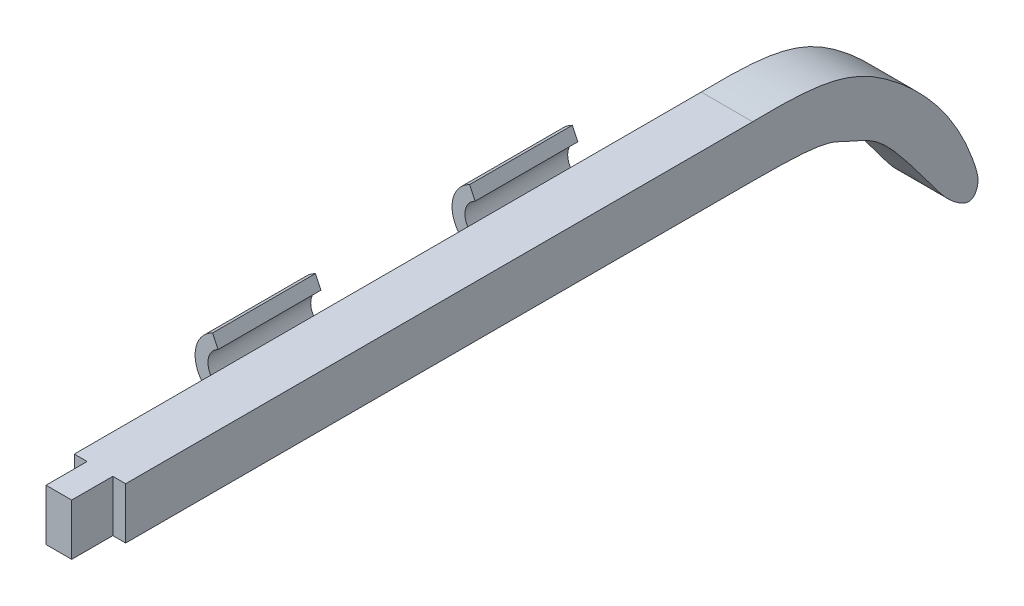
SolidWorks part; units mm, degrees
ref_plane "Front Plane" through (0, 0, 0) normal (0, 0, 1) x (1, 0, 0)
ref_plane "Top Plane" through (0, 0, 0) normal (0, 1, 0) x (1, 0, 0)
ref_plane "Right Plane" through (0, 0, 0) normal (1, 0, 0) x (0, 0, -1)
sketch "Sketch3" plane through (0, 0, 0) normal (1, 0, 0) x (0, 0, -1)
  line L2 (0, 10) -> (130, 10)
  line L4 (0, 0) -> (0, 10)
  line L6 (130, 0) -> (0, 0)
  spline S0 degree 3 poles (130, 10) (143.2578, 10.296) (152.3626, 8.4113) (167.4786, -5.7733) (172.6159, -16.2821) (174.0748, -21.8732) (172.8579, -25.2751) (168.5616, -23.1552) (157.0615, -7.4485) (154.6005, -5.1266) (145.2323, -1.2395) (144.4774, 0) (130, 0) knots 0 0 0 0 0.101519 0.157911 0.210542 0.223356 0.22806 0.254301 0.29921 0.632235 0.706477 1 1 1 1
  point P0 (155.8873, 4.2546)
  dimension "D1" = 130
  dimension "D5" = 10
ref_plane "Plane3" through (0, 0, -50) normal (0, 0, 1) x (1, 0, 0)
ref_plane "Plane4" through (0, 0, -75) normal (0, 0, 1) x (1, 0, 0)
extrude "Boss-Extrude1" add sketch "Sketch3" along normal blind 10 contours L2 S0 L6 L4
sketch "Sketch6" plane through (0, 0, -50) normal (0, 0, 1) x (1, 0, 0)
  line L3 (-2.4913, 6.4583) -> (-6.5099, 14.8705) construction
  line L9 (0, 10) -> (0, 0)
  line L11 (0, 0) -> (0, 10) construction
  arc A3 (-4, 9.6165) -> (0, 4) centre (-2.4913, 6.4583) ccw
  arc A4 (-5.0776, 11.8723) -> (-5.9318, 11.3739) centre (-2.4913, 6.4583) ccw
  arc A5 (-4.2269, 3.4189) -> (0, 4) centre (-2.4913, 6.4583) ccw
  arc A6 (-5.9318, 11.3739) -> (0, 1) centre (-2.4913, 6.4583) ccw
  arc A7 (-4, 9.6165) -> (-4.2269, 3.4189) centre (-2.4913, 6.4583) ccw
  arc A8 (-4, 9.6165) -> (0, 4) centre (-2.4913, 6.4583) ccw
  point P0 (-5.9318, 11.3739)
  point P27 (0, 0)
  point P28 (0, 0)
  point P29 (0, 8.9167)
  point P30 (0, 8.9167)
  point P31 (0.1431, 8.7626)
  dimension "D2" = 3
  dimension "D6" = 6
  dimension "D10" = 3.5
  dimension "D7" = 4
  dimension "D8" = 1
extrude "Boss-Extrude2" add sketch "Sketch6" against normal mid plane 20 contours A3 L3 A4 A6 L9 region at (-6.1311, 6.5916, -50)
mirror "Mirror4" about plane through (0, 0, -75) normal (0, 0, 1) of "Boss-Extrude2"
sketch "Sketch7" plane through (0, 0, 0) normal (0, 0, 1) x (1, 0, 0)
  line L0 (10, 10) -> (0, 10) construction
  line L1 (7.5, 10) -> (2.5, 10)
  line L2 (7.5, 10) -> (7.5, 0)
  line L3 (7.5, 0) -> (2.5, 0)
  line L4 (2.5, 10) -> (2.5, 0)
  line L5 (10, 0) -> (0, 0) construction
  line L6 (10, 0) -> (10, 10) construction
  line L7 (0, 0) -> (0, 10) construction
  line L8 (10, 0) -> (10, 10)
  line L9 (10, 0) -> (0, 0)
  line L10 (0, 0) -> (0, 10)
  line L11 (10, 10) -> (0, 10)
  point P8 (5, 10)
  point P9 (5, 10)
  line M5 (0, 10) -> (0, 0)
  line M6 (0, 0) -> (10, 0)
  line M7 (10, 0) -> (10, 10)
  line M8 (10, 10) -> (0, 10)
  dimension "D1" = 5
extrude "Cut-Extrude1" cut sketch "Sketch7" against normal blind 8 contours L2 M8 M6 M7 | L4 M8 M5 M6 region at (8.75, 5, 0) region at (1.25, 5, 0)
